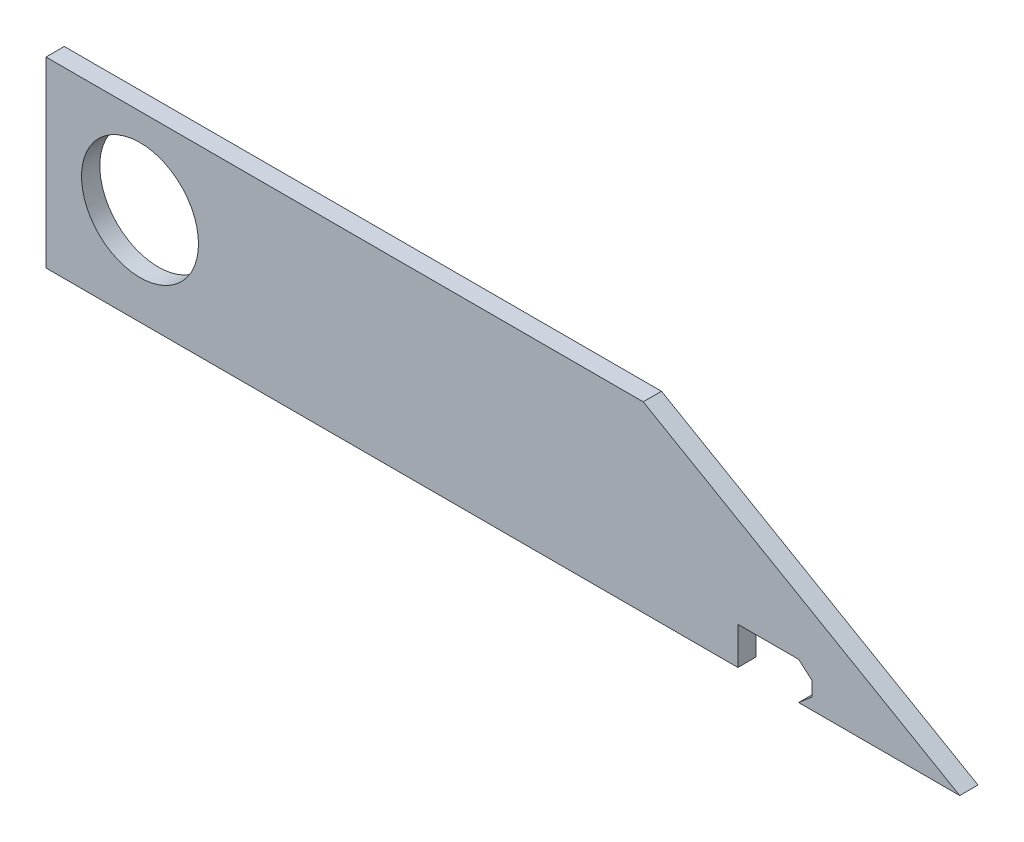
SolidWorks part; units mm, degrees
ref_plane "Front Plane" through (0, 0, 0) normal (0, 0, 1) x (1, 0, 0)
ref_plane "Top Plane" through (0, 0, 0) normal (0, 1, 0) x (1, 0, 0)
ref_plane "Right Plane" through (0, 0, 0) normal (1, 0, 0) x (0, 0, -1)
sketch "Sketch2" plane through (0, 0, 0) normal (0, 0, 1) x (1, 0, 0)
  line L0 (-63.5, 2.4) -> (63.5, 2.4)
  line L1 (63.5, 2.4) -> (19.5059, 27.8)
  line L2 (19.5059, 27.8) -> (-63.5, 27.8)
  line L3 (-63.5, 27.8) -> (-63.5, 2.4)
  line L4 (65.5, 5.8641) -> (63.5, 2.4) construction
  point P7 (0, 0)
  dimension "D1" = 25.4
  dimension "D2" = 30
extrude "Boss-Extrude1" add sketch "Sketch2" against normal blind 2.54
sketch "Sketch3" plane through (0, 0, 0) normal (0, 0, 1) x (1, 0, 0)
  circle A0 centre (-50.4348, 15.9061) radius 8.128
extrude "Cut-Extrude1" cut sketch "Sketch3" against normal blind 2.54
sketch "Sketch4" plane through (0, 0, -2.54) normal (0, 0, -1) x (-1, 0, 0)
  line L0 (-41.1054, 7.6) -> (-32.6673, 7.6)
  line L1 (-32.6673, 7.6) -> (-32.6673, 2.4)
  line L2 (63.5, 2.4) -> (-63.5, 2.4) construction
  line L3 (-32.6673, 7.6) -> (-32.6673, 2.4) construction
  line L4 (-32.6673, 2.4) -> (-41.1054, 2.4)
  line L5 (-41.1054, 2.4) -> (-42.9673, 4) construction
  line L6 (-41.1054, 2.4) -> (-42.9673, 4)
  line L7 (-42.9673, 4) -> (-42.9673, 6)
  line L8 (-42.9673, 6) -> (-41.1054, 7.6) construction
  line L9 (-42.9673, 4) -> (-42.9673, 6) construction
  line L10 (-42.9673, 6) -> (-41.1054, 7.6)
extrude "Cut-Extrude2" cut sketch "Sketch4" against normal through all
